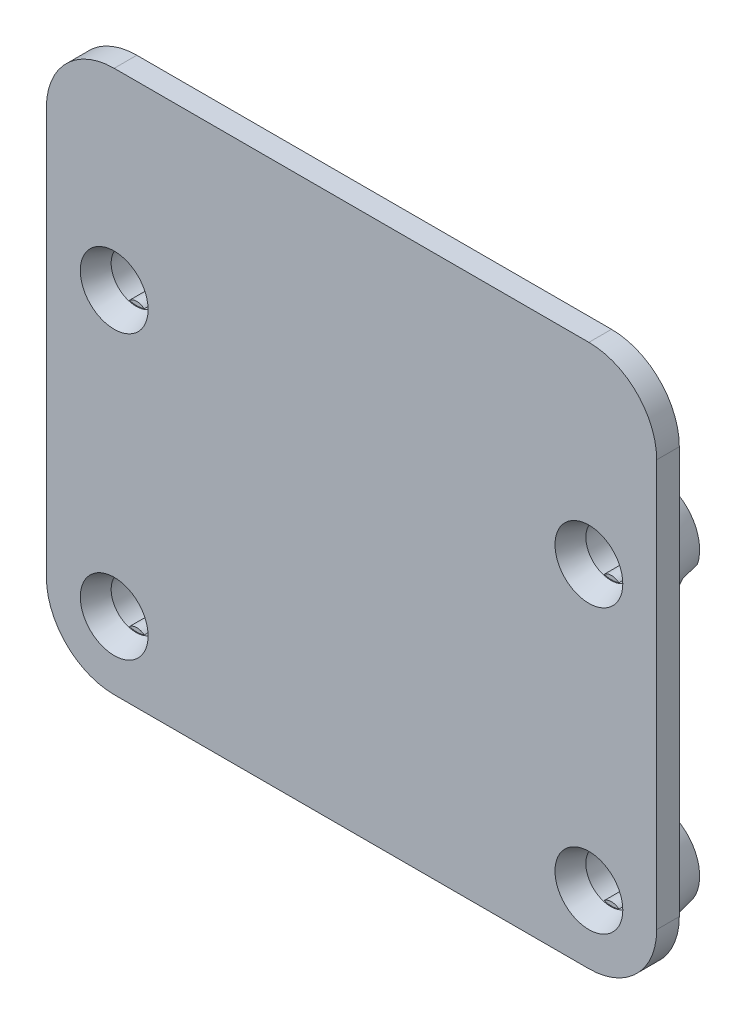
SolidWorks part; units mm, degrees
ref_plane "Front Plane" through (0, 0, 0) normal (0, 0, 1) x (1, 0, 0)
ref_plane "Top Plane" through (0, 0, 0) normal (0, 1, 0) x (1, 0, 0)
ref_plane "Right Plane" through (0, 0, 0) normal (1, 0, 0) x (0, 0, -1)
sketch "Sketch1" plane through (0, 0, 0) normal (0, 0, 1) x (1, 0, 0)
  line L0 (0, 12) -> (0, -12) construction
  line L1 (10.5, 12) -> (-10.5, 12)
  line L2 (13.5, 9) -> (13.5, -9)
  line L3 (10.5, -12) -> (-10.5, -12)
  line L4 (-13.5, 9) -> (-13.5, -9)
  line L5 (10.5, -2.75) -> (-10.5, -2.75) construction
  line L6 (-10.5, -9) -> (-10.5, 3.5) construction
  line L7 (10.5, 3.5) -> (10.5, -9) construction
  arc A0 (-10.5, -12) -> (-13.5, -9) centre (-10.5, -9) cw
  arc A1 (-10.5, 12) -> (-13.5, 9) centre (-10.5, 9) ccw
  arc A2 (10.5, 12) -> (13.5, 9) centre (10.5, 9) cw
  arc A3 (13.5, -9) -> (10.5, -12) centre (10.5, -9) cw
  point P4 (10.5, 3.5)
  point P5 (10.5, -9)
  point P6 (0, 0)
  point P7 (-10.5, -9)
  point P9 (-10.5, 3.5)
  point P17 (-13.5, -12)
  point P20 (-13.5, 12)
  point P26 (0, 0)
  dimension "D4" = 3
  dimension "D1" = 3
  dimension "D2" = 3
  dimension "D3" = 24
  dimension "D5" = 21
  dimension "D6" = 12.5
extrude "Boss-Extrude1" add sketch "Sketch1" along normal blind 1
sketch "Sketch4" plane through (0, 0, 0) normal (0, 0, -1) x (-1, 0, 0)
  circle A0 centre (-10.5, 3.5) radius 2.3
  circle A1 centre (10.5, 3.5) radius 2.3
  circle A2 centre (10.5, -9) radius 2.3
  circle A3 centre (-10.5, -9) radius 2.3
  dimension "D1" = 4.6
extrude "Boss-Extrude2" add sketch "Sketch4" along normal blind 2
hole_wizard "M2 Clearance Hole1" positions "Sketch2" profile "Sketch3" hole size "M2" standard "ISO" end condition through all
sketch "Sketch2" plane through (0, 0, 1) normal (0, 0, 1) x (1, 0, 0)
  point P0 (10.5, 3.5)
  point P2 (10.5, -9)
  point P4 (-10.5, -9)
  point P6 (-10.5, 3.5)
  point P13 (0, 0)
  point P14 (0, 0)
sketch "Sketch3" plane through (10.5, 3.5, 1) normal (1, 0, 0) x (0, -1, 0)
  line L0 (0, 0) -> (0, 3)
  line L1 (0, 3) -> (1.1, 3)
  line L2 (1.1, 3) -> (1.1, 0.9657)
  line L3 (1.1, 0.9657) -> (1.5, 0)
  line L5 (1.5, 0) -> (0, 0)
  line L6 (-1.1, 0.9657) -> (-1.5, 0) construction
  line L11 (0, -6.35) -> (0, 107.95) construction
  dimension "Thru Hole Dia." = 2.2
  dimension "Thru Hole Depth" = 3
  dimension "Near C'Sink Dia." = 3
  dimension "Near C'Sink Angle" = 45
sketch "Sketch6" plane through (0, 0, 1) normal (0, 0, 1) x (1, 0, 0)
  line L0 (8.0915, 2.4) -> (12.5968, 2.4) construction
  line L1 (8.3943, 2.57) -> (12.5968, 2.57) construction
  line L2 (10.5, 3.5) -> (10.5, -9) construction
  line L3 (8.1393, 3.5) -> (12.671, 3.5) construction
  line L4 (8.3943, 4.43) -> (12.5968, 4.43) construction
  line L5 (8.0915, 4.6) -> (12.5968, 4.6) construction
  line L6 (10.1244, 2.4) -> (10.8756, 2.4)
  line L7 (10.1244, 4.6) -> (10.8756, 4.6)
  line L8 (-10.5, -2.75) -> (10.5, -2.75) construction
  line L9 (0, -12) -> (0, 12.0448) construction
  line L10 (-10.5, -12) -> (10.5, -12) construction
  line L11 (10.5, -2.75) -> (-10.5, -2.75) construction
  line L12 (-10.5, -9) -> (-10.5, 3.5) construction
  line L13 (-10.1244, 2.4) -> (-10.8756, 2.4)
  line L14 (-10.1244, 4.6) -> (-10.8756, 4.6)
  line L15 (10.1244, -10.1) -> (10.8756, -10.1)
  line L16 (10.1244, -7.9) -> (10.8756, -7.9)
  line L17 (-10.1244, -10.1) -> (-10.8756, -10.1)
  line L18 (-10.1244, -7.9) -> (-10.8756, -7.9)
  arc A0 (10.8756, 4.6) -> (10.1244, 4.6) centre (10.5, 4.93) cw
  circle A1 centre (10.5, 3.5) radius 1.1 construction
  arc A2 (10.8756, 2.4) -> (10.1244, 2.4) centre (10.5, 2.07) ccw
  arc A3 (-10.8756, 2.4) -> (-10.1244, 2.4) centre (-10.5, 2.07) cw
  arc A4 (-10.8756, 4.6) -> (-10.1244, 4.6) centre (-10.5, 4.93) ccw
  arc A5 (10.8756, -10.1) -> (10.1244, -10.1) centre (10.5, -10.43) ccw
  arc A6 (10.8756, -7.9) -> (10.1244, -7.9) centre (10.5, -7.57) cw
  arc A7 (-10.8756, -10.1) -> (-10.1244, -10.1) centre (-10.5, -10.43) cw
  arc A8 (-10.8756, -7.9) -> (-10.1244, -7.9) centre (-10.5, -7.57) ccw
  point P30 (0, 0)
  point P31 (0, 0)
  dimension "D1" = 1.86
  dimension "D2" = 0.5
extrude "Boss-Extrude3" add sketch "Sketch6" against normal blind 0.75 from offset 1 offset against normal yes
chamfer "Chamfer1" distance 2 distance2 0.4 4 edges at (-12.8, -9, -2) (-12.8, 3.5, -2) (8.2, 3.5, -2) (8.2, -9, -2) first distance on face at (-12.8, -9, -2) first distance on face at (-12.8, 3.5, -2) first distance on face at (8.2, 3.5, -2) first distance on face at (8.2, -9, -2)
sketch "Sketch5" plane through (0, 0, -2) normal (0, 0, -1) x (-1, 0, 0)
  line L0 (8.7126, 4.9474) -> (10.5, 3.5)
  line L1 (10.5, 3.5) -> (9.1808, 1.616)
  line L2 (10.4197, -11.2986) -> (10.5, -9)
  line L3 (10.5, -9) -> (8.2589, -9.5174)
  line L4 (-12.6747, 2.7512) -> (-10.5, 3.5)
  line L5 (-10.5, 3.5) -> (-10.7404, 1.2126)
  line L6 (-10.5, -6.7) -> (-10.5, -9)
  line L7 (-10.5, -9) -> (-8.2004, -8.9599)
  line L8 (-10.5, 3.5) -> (-10.5, -9) construction
  line L9 (10.5, 3.5) -> (10.5, -9) construction
  arc A0 (8.7126, 4.9474) -> (9.1808, 1.616) centre (10.5, 3.5) ccw
  circle A1 centre (10.5, 3.5) radius 2.3 construction
  arc A2 (8.2589, -9.5174) -> (10.4197, -11.2986) centre (10.5, -9) ccw
  circle A3 centre (10.5, -9) radius 2.3 construction
  arc A4 (-10.5, -6.7) -> (-8.2004, -8.9599) centre (-10.5, -9) cw
  circle A5 centre (-10.5, -9) radius 2.3 construction
  arc A6 (-12.6747, 2.7512) -> (-10.7404, 1.2126) centre (-10.5, 3.5) ccw
  circle A7 centre (-10.5, 3.5) radius 2.3 construction
  point P9 (0, 0)
  point P21 (-8.2791, -8.1569)
  point P25 (0, 0)
  dimension "D1" = 35
  dimension "D2" = 94
  dimension "D3" = 103
  dimension "D4" = 75
  dimension "D5" = 6
  dimension "D6" = 65
  dimension "D7" = 89
extrude "Cut-Extrude2" cut sketch "Sketch5" against normal blind 0.8
